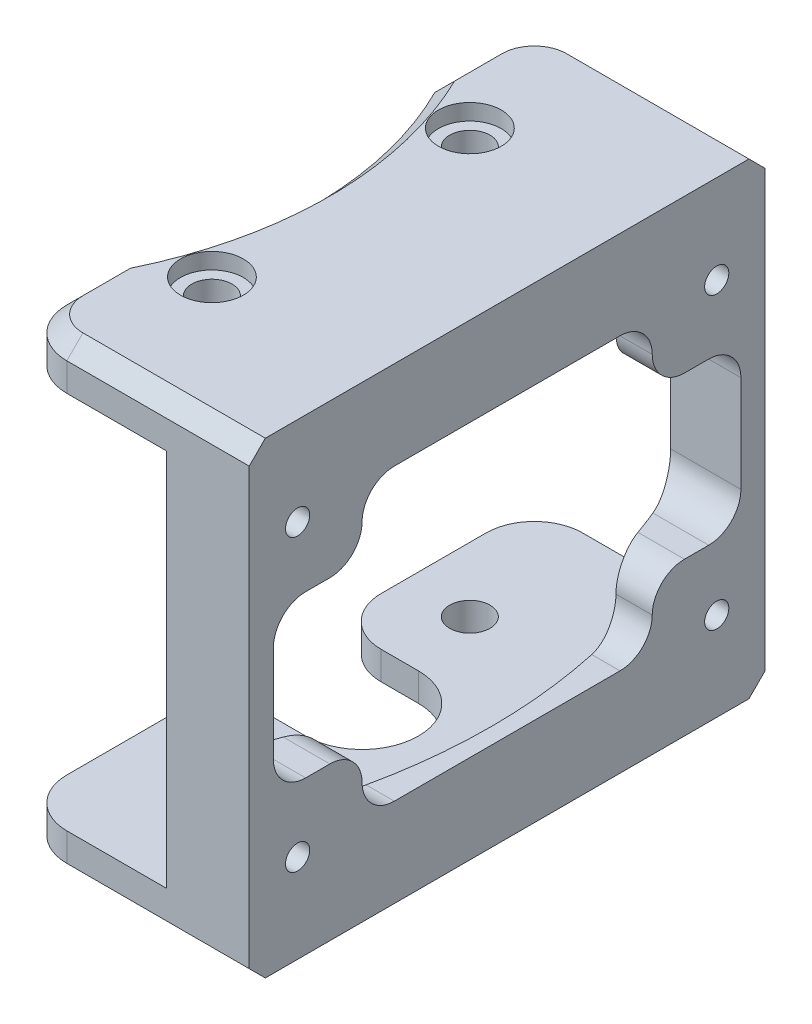
SolidWorks part; units mm, degrees
ref_plane "Спереди" through (0, 0, 0) normal (0, 0, 1) x (1, 0, 0)
ref_plane "Сверху" through (0, 0, 0) normal (0, 1, 0) x (1, 0, 0)
ref_plane "Справа" through (0, 0, 0) normal (1, 0, 0) x (0, 0, -1)
sketch "Эскиз1" plane through (0, 0, 0) normal (0, 1, 0) x (1, 0, 0)
  line L1 (19.6854, 16) -> (34, 16)
  line L2 (19.6854, 16) -> (19.6854, -16)
  line L3 (19.6854, -16) -> (34, -16)
  line L4 (34, 16) -> (34, -16)
  line L5 (19.6854, 16) -> (34, -16) construction
  line L6 (19.6854, -16) -> (34, 16) construction
  line L7 (23.6854, 8) -> (23.6854, -8) construction
  circle A0 centre (0, 0) radius 25 construction
  circle A1 centre (23.6854, 8) radius 1.25
  circle A2 centre (23.6854, -8) radius 1.25
  point P3 (26.8427, 0)
  dimension "D1" = 50
  dimension "D6" = 2.5
  dimension "D7" = 2.5
  dimension "D2" = 32
  dimension "D3" = 34
  dimension "D4" = 16
  dimension "D5" = 4
extrude "Бобышка-Вытянуть1" add sketch "Эскиз1" along normal mid plane 29
sketch "Эскиз2" plane through (0, 0, 0) normal (0, 1, 0) x (1, 0, 0)
  circle A0 centre (0, 0) radius 33
  dimension "D1" = 66
extrude "Вырез-Вытянуть1" cut sketch "Эскиз2" against normal mid plane 23.5
sketch "Эскиз3" plane through (34, 0, 0) normal (1, 0, 0) x (0, 0, -1)
  line L0 (-13, 5) -> (-9, 5)
  line L1 (13, 9) -> (-13, 9) construction
  line L2 (13, 9) -> (13, -9) construction
  line L3 (13, -9) -> (-13, -9) construction
  line L4 (-13, 9) -> (-13, -9) construction
  line L5 (13, 9) -> (-13, -9) construction
  line L6 (13, -9) -> (-13, 9) construction
  line L7 (-9, 5) -> (-9, 9)
  line L8 (-13, 0) -> (13, 0) construction
  line L9 (0, 9) -> (0, -9) construction
  line L10 (-9, -5) -> (-9, -9)
  line L11 (-13, -5) -> (-9, -5)
  line L12 (-13, 5) -> (-13, -5)
  line L13 (9, -5) -> (9, -9)
  line L14 (13, -5) -> (9, -5)
  line L15 (13, 5) -> (13, -5)
  line L16 (13, 5) -> (9, 5)
  line L17 (9, 5) -> (9, 9)
  line L18 (-9, 9) -> (9, 9)
  line L19 (9, -9) -> (-9, -9)
  circle A0 centre (-13, 9) radius 0.75
  circle A1 centre (-13, -9) radius 0.75
  circle A2 centre (13, 9) radius 0.75
  circle A3 centre (13, -9) radius 0.75
  point P0 (0, 0)
  dimension "D5" = 1.5
  dimension "D6" = 1.5
  dimension "D7" = 1.5
  dimension "D8" = 1.5
  dimension "D1" = 18
  dimension "D2" = 26
  dimension "D3" = 4
  dimension "D4" = 4
extrude "Вырез-Вытянуть2" cut sketch "Эскиз3" against normal through all
sketch "Эскиз4" plane through (0, -14.5, 0) normal (0, -1, 0) x (1, 0, 0)
  line L0 (19.6854, -16) -> (19.6854, 16) construction
  line L1 (25, 3.5) -> (19.6854, 3.5)
  line L2 (25, 3.5) -> (25, -3.5) construction
  line L3 (25, -3.5) -> (19.6854, -3.5)
  line L4 (19.6854, 3.5) -> (19.6854, -3.5)
  circle A0 centre (0, 0) radius 25 construction
  circle A1 centre (25, 0) radius 3.5
  line M9 (19.6854, 16) -> (19.6854, -16)
  dimension "D1" = 50
  dimension "D2" = 7
extrude "Вырез-Вытянуть3" cut sketch "Эскиз4" against normal up to next contours A1 L1 L3 M9 | A1 region at (21.0872, -14.5, 0) region at (25, -14.5, 0)
sketch "Эскиз6" plane through (0, 14.5, 0) normal (0, 1, 0) x (1, 0, 0)
  circle A0 centre (0, 0) radius 22
  dimension "D1" = 44
extrude "Вырез-Вытянуть5" cut sketch "Эскиз6" against normal up to next
sketch "Эскиз7" plane through (34, 0, 0) normal (1, 0, 0) x (0, 0, -1)
  line L0 (-9, 5) -> (-13, 5) construction
  line L1 (14.5, 5) -> (-14.5, 5)
  line L2 (14.5, 5) -> (14.5, -5)
  line L3 (14.5, -5) -> (-14.5, -5)
  line L4 (-14.5, 5) -> (-14.5, -5)
  line L5 (14.5, 5) -> (-14.5, -5) construction
  line L6 (14.5, -5) -> (-14.5, 5) construction
  line L7 (-13, 5) -> (-13, -5) construction
  point P0 (0, 0)
  dimension "D1" = 1.5
extrude "Вырез-Вытянуть6" cut sketch "Эскиз7" against normal through all
fillet "Скругление1" radius 3 6 edges at (19.6854, -13.125, 3.5) (19.6854, -13.125, -3.5) (19.6854, -13.125, -16) (19.6854, 13.125, -16) (19.6854, 13.125, 16) (19.6854, -13.125, 16)
fillet "Скругление3" radius 2 12 edges at (32.8745, -5, 9) (32.8745, -9, 9) (32.8745, -9, -9) (32.8745, -5, -9) (32.8745, 5, -9) (32.8745, 9, -9) (32.8745, 9, 9) (32.8745, 5, 9) (31.8219, 5, -14.5) (31.8219, -5, -14.5) (31.8219, -5, 14.5) (31.8219, 5, 14.5)
chamfer "Фаска2" distance 1 angle 45 17 edges at (28.3427, -14.5, 16) (20.5641, -14.5, 15.1213) (19.6854, -14.5, 9.75) (20.5641, -14.5, 4.3787) (23.8427, -14.5, 3.5) (28.5, -14.5, 0) (23.8427, -14.5, -3.5) (20.5641, -14.5, -4.3787) (19.6854, -14.5, -9.75) (20.5641, -14.5, -15.1213) (28.3427, -14.5, -16) (28.3427, 14.5, 16) (20.5641, 14.5, 15.1213) (20.5641, 14.5, -15.1213) (28.3427, 14.5, -16) (22, 14.5, 0) (19.6854, 14.5, 11.4113)
sketch "Эскиз5" plane through (0, 14.5, 0) normal (0, 1, 0) x (1, 0, 0)
  circle A0 centre (23.6854, 8) radius 1.95
  circle A1 centre (23.6854, -8) radius 1.95
  dimension "D1" = 3.9
  dimension "D2" = 3.9
extrude "Вырез-Вытянуть4" cut sketch "Эскиз5" against normal blind 1
mirror "Зеркальное отражение1" about plane through (0, 0, 0) normal (0, 1, 0) of "Вырез-Вытянуть4"
equation "\"motor_diameter\"= 30"
equation "\"mm_diameter\"= IIF ( \"motor_diameter\" < 34 , 41 , \"motor_diameter\" + 8 )"
equation "\"upper_shafts_diameter\"= 5"
equation "\"upper_shats_length\"= 180"
equation "\"upper_bearing_d1\"= 10"
equation "\"upper_bearing_d2\"= 5"
equation "\"upper_bearing_h\"= 15"
equation "\"lower_shafts_diameter\"= 5"
equation "\"lower_shafts_length\"= 180"
equation "\"lower_bearing_d1\"= 10"
equation "\"lower_bearing_d2\"= 5"
equation "\"lower_bearing_h\"= 15"
equation "\"print_offset\"= 0.5"
equation "\"bh_screws_d\"= 2"
equation "\"bh_screws_h\"= 20"
equation "\"bh_screws_hh_d\"= 3.4"
equation "\"bh_screws_hh_h\"= 2"
equation "\"bh_nut_d\"= 3.8"
equation "\"bh_nut_h\"= 2"
equation "\"motor_screws_d\"= 3"
equation "\"motor_screws_h\"= 16"
equation "\"motor_screws_hh_d\"= 5.5"
equation "\"motor_screws_hh_h\"= 3"
equation "\"plate_hole_distance\"= 25.4"
equation "\"plate_screws_d\"= 6.5"
equation "\"shafts_diameter\"= IIF ( \"mm_diameter\" < 42 , 42 + 8 , \"mm_diameter\" + 8 )"
equation "\"central_hole_diameter\"= 8"
equation "\"bh_thikness\"= 4"
equation "\"ends_screws_d\"= 4"
equation "\"ends_screws_h\"= 16"
equation "\"ends_screws_hh_d\"= 6.7"
equation "\"ends_screws_hh_h\"= 4.1"
equation "\"ends_nut_d\"= 6.8"
equation "\"ends_nut_h\"= 3"
equation "\"system_radius\" = ( \"shafts_diameter\" + 12 + \"bh_thikness\" / 2 ) / 2"
equation "\"encoder_distance\"= \"system_radius\" + 4"
equation "\"tape_position\"= \"encoder_distance\" - 2 + 3.9 + 1.7 / 2"
equation "\"D1@Эскиз1\"=\"shafts_diameter\""
equation "\"D3@Эскиз1\"=\"encoder_distance\"-2"
equation "\"D5@Эскиз1\"=\"bh_thikness\""
equation "\"D6@Эскиз1\"=\"bh_screws_d\"+\"print_offset\""
equation "\"D7@Эскиз1\"=\"bh_screws_d\"+\"print_offset\""
equation "\"D1@Бобышка-Вытянуть1\"=\"upper_bearing_h\"+\"bh_thikness\"*2+6"
equation "\"D1@Эскиз2\"=\"system_radius\"*2+2"
equation "\"D1@Вырез-Вытянуть1\"=\"upper_bearing_h\"+\"bh_thikness\"*2+\"print_offset\""
equation "\"D5@Эскиз3\"=\"bh_screws_d\"-\"print_offset\""
equation "\"D6@Эскиз3\"=\"D5@Эскиз3\""
equation "\"D7@Эскиз3\"=\"D6@Эскиз3\""
equation "\"D8@Эскиз3\"=\"D5@Эскиз3\""
equation "\"D1@Эскиз4\"=\"shafts_diameter\""
equation "\"D2@Эскиз4\"=\"lower_shafts_diameter\"+2"
equation "\"D1@Эскиз5\"=\"bh_screws_hh_d\"+\"print_offset\""
equation "\"D2@Эскиз5\"=\"D1@Эскиз5\""
equation "\"D1@Эскиз6\"= IIF ( \"mm_diameter\" < 42 , 44 , \"mm_diameter\" + 2 )"
